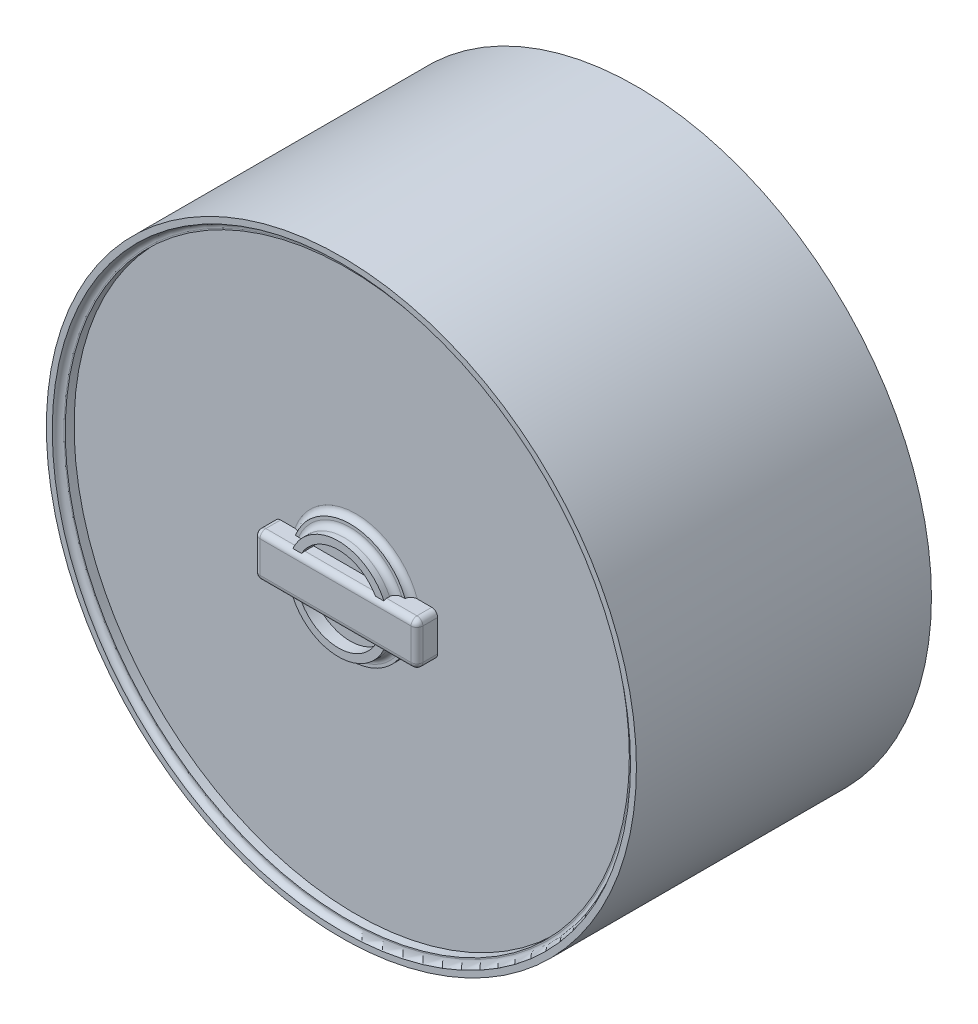
SolidWorks part; units mm, degrees
ref_plane "Front Plane" through (0, 0, 0) normal (0, 0, 1) x (1, 0, 0)
ref_plane "Top Plane" through (0, 0, 0) normal (0, 1, 0) x (1, 0, 0)
ref_plane "Right Plane" through (0, 0, 0) normal (1, 0, 0) x (0, 0, -1)
sketch "Sketch2" plane through (0, 0, 0) normal (0, 0, 1) x (1, 0, 0)
  circle A0 centre (0, 0) radius 500
extrude "Boss-Extrude1" add sketch "Sketch2" along normal blind 250 and the other way blind 250
sketch "Sketch3" plane through (0, 0, 250) normal (0, 0, 1) x (1, 0, 0)
  circle A0 centre (0, 0) radius 490
  dimension "D1" = 980
extrude "Cut-Extrude4" cut sketch "Sketch3" against normal blind 10
sketch "Sketch5" plane through (0, 0, 240) normal (0, 0, 1) x (1, 0, 0)
  circle A0 centre (0, 0) radius 478
extrude "Cut-Extrude5" cut sketch "Sketch5" against normal blind 15
sketch "Sketch6" plane through (0, 0, 225) normal (0, 0, 1) x (1, 0, 0)
  circle A0 centre (0, 0) radius 100
extrude "Boss-Extrude2" add sketch "Sketch6" along normal blind 10
sketch "Sketch7" plane through (0, 0, 235) normal (0, 0, 1) x (1, 0, 0)
  circle A0 centre (0, 0) radius 85
extrude "Boss-Extrude3" add sketch "Sketch7" along normal blind 20
sketch "Sketch8" plane through (0, 0, 255) normal (0, 0, 1) x (1, 0, 0)
  circle A0 centre (0, 0) radius 72
extrude "Cut-Extrude6" cut sketch "Sketch8" against normal blind 20
fillet "Fillet2" radius 10 1 edges at (85, 0, 235)
ref_plane "Plane1" through (0, 0, 220) normal (0, 0, 1) x (1, 0, 0)
sketch "Sketch9" plane through (0, 0, 220) normal (0, 0, 1) x (1, 0, 0)
  line L1 (-138.0836, 36.7481) -> (138.0836, 36.7481)
  line L2 (-138.0836, 36.7481) -> (-138.0836, -36.7481)
  line L3 (-138.0836, -36.7481) -> (138.0836, -36.7481)
  line L4 (138.0836, 36.7481) -> (138.0836, -36.7481)
  line L5 (-138.0836, 36.7481) -> (138.0836, -36.7481) construction
  line L6 (-138.0836, -36.7481) -> (138.0836, 36.7481) construction
  point P0 (0, 0)
extrude "Boss-Extrude4" add sketch "Sketch9" along normal blind 40
fillet "Fillet3" radius 10 8 edges at (0, -36.7481, 260) (-138.0836, 0, 260) (0, 36.7481, 260) (138.0836, 0, 260) (138.0836, 36.7481, 242.5) (138.0836, -36.7481, 242.5) (-138.0836, -36.7481, 242.5) (-138.0836, 36.7481, 242.5)
fillet "Fillet4" radius 10 1 edges at (0, 100, 225)
fillet "Fillet5" radius 10 1 edges at (490, 0, 240)
sketch "Sketch10" plane through (0, 0, -250) normal (0, 0, -1) x (-1, 0, 0)
  circle A0 centre (0, 0) radius 100
  dimension "D1" = 200
extrude "Boss-Extrude5" add sketch "Sketch10" along normal blind 10
scale "Scale1" scale about centroid uniform scaling yes scale factor 0.7
